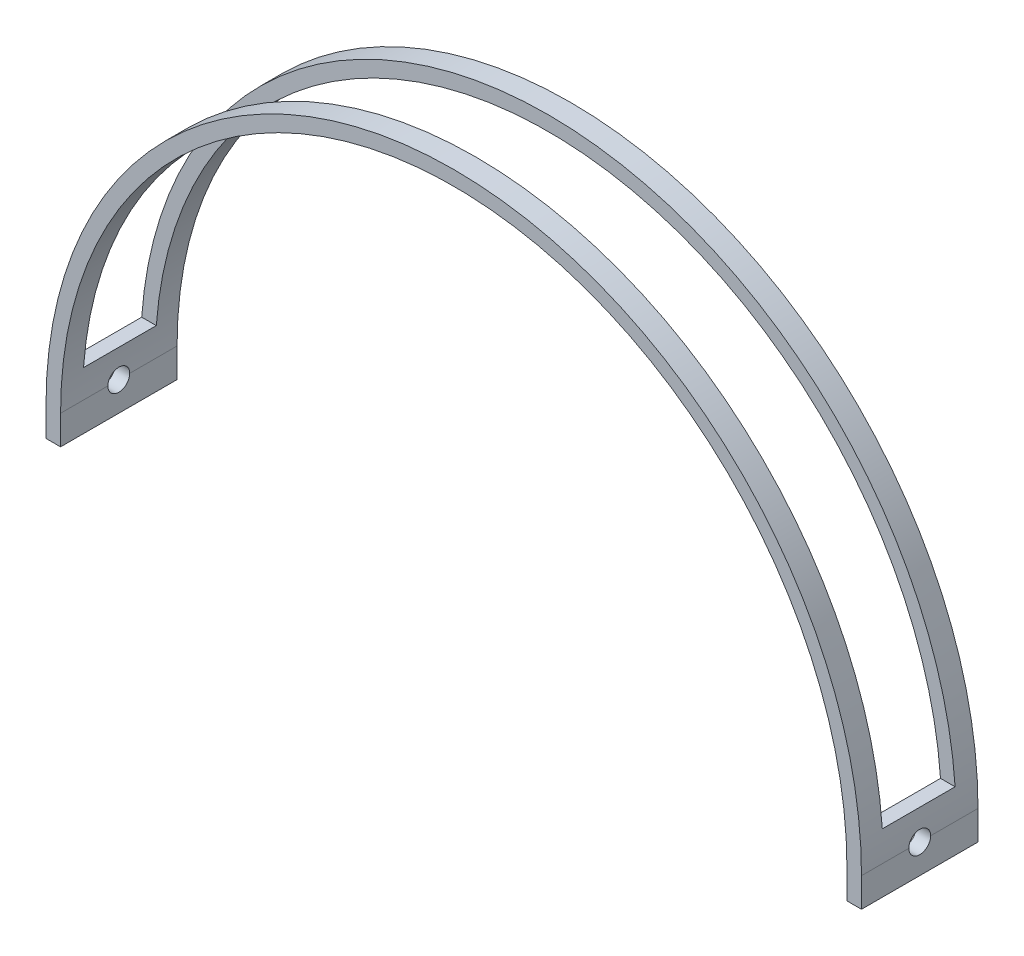
SolidWorks part; units mm, degrees
ref_plane "Front Plane" through (0, 0, 0) normal (0, 0, 1) x (1, 0, 0)
ref_plane "Top Plane" through (0, 0, 0) normal (0, 1, 0) x (1, 0, 0)
ref_plane "Right Plane" through (0, 0, 0) normal (1, 0, 0) x (0, 0, -1)
sketch "Sketch1" plane through (0, 0, 0) normal (0, 0, 1) x (1, 0, 0)
  line L0 (-280, 0) -> (280, 0) construction
  line L3 (-280, 0) -> (-280, -20)
  line L4 (-280, -20) -> (-270, -20)
  line L5 (-270, 0) -> (-270, -20)
  line L7 (270, 0) -> (270, -20)
  line L8 (270, -20) -> (280, -20)
  line L9 (280, 0) -> (280, -20)
  arc A0 (280, 0) -> (-280, 0) centre (0, 0) ccw
  arc A1 (270, 0) -> (-270, 0) centre (0, 0) ccw
  dimension "D1" = 270
  dimension "D2" = 280
  dimension "D3" = 20
extrude "Boss-Extrude1" add sketch "Sketch1" along normal blind 80
sketch "Sketch2" plane through (280, 0, 0) normal (1, 0, 0) x (0, 0, -1)
  line L0 (-80, 0) -> (0, 0) construction
  circle A0 centre (-40, 0) radius 7.5
  dimension "D1" = 15
extrude "Cut-Extrude2" cut sketch "Sketch2" against normal through all
sketch "Sketch4" plane through (280, 0, 0) normal (1, 0, 0) x (0, 0, -1)
  line L0 (-40, 280) -> (-40, 7.5) construction
  line L1 (0, 280) -> (-80, 280) construction
  line L4 (-65, 20) -> (-65, 280)
  line L5 (-65, 280) -> (-15, 280)
  line L6 (-15, 280) -> (-15, 20)
  line L8 (-32.5, 0) -> (0, 0) construction
  line L13 (-65, 20) -> (-15, 20)
  arc A1 (-32.5, 0) -> (-47.5, 0) centre (-40, 0) ccw construction
  dimension "D1" = 50
  dimension "D2" = 20
extrude "Cut-Extrude3" cut sketch "Sketch4" against normal through all
ref_point "Point1"
ref_point "Point2"
ref_axis "Axis1" through (-274.9744, 0.0003, 40) along (1, 0, 0)
